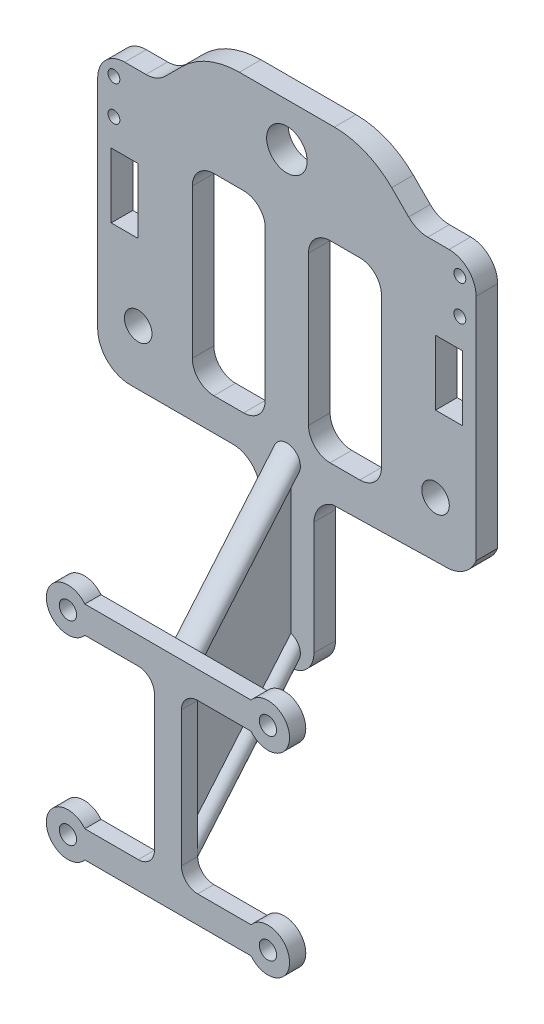
SolidWorks part; units mm, degrees
ref_plane "Спереди" through (0, 0, 0) normal (0, 0, 1) x (1, 0, 0)
ref_plane "Сверху" through (0, 0, 0) normal (0, 1, 0) x (1, 0, 0)
ref_plane "Справа" through (0, 0, 0) normal (1, 0, 0) x (0, 0, -1)
sketch "Model" plane through (0, 0, 0) normal (0, 0, 1) x (1, 0, 0)
  line L0 (-32.5, 1.0025) -> (-27.5, 1.0025)
  line L1 (-27.5, 1.0025) -> (-27.5, 11.0025)
  line L2 (-27.5, 11.0025) -> (-32.5, 11.0025)
  line L3 (-32.5, 11.0025) -> (-32.5, 1.0025)
  line L4 (32.5, 11.0025) -> (27.5, 11.0025)
  line L5 (27.5, 11.0025) -> (27.5, 1.0025)
  line L6 (27.5, 1.0025) -> (32.5, 1.0025)
  line L7 (32.5, 1.0025) -> (32.5, 11.0025)
  line L8 (-8.7868, 34.9967) -> (8.7868, 34.9967)
  line L9 (35, 8.7835) -> (35, -21.3839)
  line L11 (5, -30.1878) -> (5, -51.1878)
  line L12 (0.5, -55.6878) -> (-0.5, -55.6878)
  line L13 (-5, -51.1878) -> (-5, -30.1878)
  line L14 (8.4254, -25.669) -> (29, -25.1878)
  line L16 (-15.452, -19.1878) -> (15.452, -19.1878)
  line L17 (-17.5, -3.7682) -> (-17.5, -19.1878) construction
  line L18 (-17.5, -19.1878) -> (-15.452, -19.1878) construction
  line L19 (17.5, 14.8517) -> (17.5, 16.4118) construction
  line L20 (-27.5, 26.9967) -> (27.5, 26.9967) construction
  line L21 (17.5, 16.4118) -> (11.2964, 16.4118) construction
  line L22 (-27.5, 26.9967) -> (-27.5, 17.8476) construction
  line L23 (27.5, 26.9967) -> (27.5, -15.0033) construction
  line L24 (-17.5, -19.1878) -> (17.5, -19.1878)
  line L25 (-17.5, -19.1878) -> (-17.5, 16.4118)
  line L26 (-27.5, -15.0033) -> (27.5, -15.0033) construction
  line L27 (-17.5, 16.4118) -> (17.5, 16.4118)
  line L28 (17.5, -19.1878) -> (17.5, 16.4118)
  line L29 (-10, 16.0025) -> (10, 16.0025) construction
  line L30 (0, -15.0033) -> (0, -40.6878) construction
  line L31 (-5, -40.6878) -> (5, -40.6878) construction
  line L32 (0, -40.6878) -> (0, -51.1878) construction
  line L33 (0, -51.1878) -> (-0.5, -51.1878) construction
  line L34 (0, -51.1878) -> (0.5, -51.1878) construction
  line L35 (-10, -30.1878) -> (-0.5, -30.1878) construction
  line L36 (-0.5, -30.1878) -> (-0.5, -51.1878) construction
  line L37 (-30.6066, 19.3901) -> (-19.3934, 30.6033)
  line L38 (-35, 14.9967) -> (-35, 34.9967) construction
  line L39 (-35, 34.9967) -> (-15, 34.9967) construction
  line L40 (30.6066, 19.3901) -> (19.3934, 30.6033)
  line L41 (0, 34.9967) -> (0, 26.9967) construction
  line L42 (-35, 8.7835) -> (-35, -19.1878)
  line L43 (-29, -25.1878) -> (-10, -25.1878)
  line L44 (-32.5, 6.0025) -> (-27.5, 6.0025) construction
  line L45 (-27.5, 16.6674) -> (-27.5, -15.0033) construction
  line L46 (-30, 6.0025) -> (-30, -5.8427) construction
  circle A4 centre (-27.5, -15.0033) radius 2.55
  circle A5 centre (27.5, 26.9967) radius 3.556 construction
  circle A7 centre (27.5, -15.0033) radius 2.55
  circle A8 centre (0, 26.9967) radius 3.75
  arc A9 (35, 8.7835) -> (30.6066, 19.3901) centre (20, 8.7835) ccw
  arc A10 (-35, 8.7835) -> (-30.6066, 19.3901) centre (-20, 8.7835) cw
  arc A11 (19.3934, 30.6033) -> (8.7868, 34.9967) centre (8.7868, 19.9967) ccw
  arc A12 (-19.3934, 30.6033) -> (-8.7868, 34.9967) centre (-8.7868, 19.9967) cw
  arc A13 (-35, -19.1878) -> (-29, -25.1878) centre (-29, -19.1878) ccw
  arc A104 (29, -25.1878) -> (35, -21.3839) centre (29.4108, -19.2019) ccw
  arc A105 (8.4254, -25.669) -> (5, -30.1878) centre (9.9948, -30.4163) ccw
  arc A106 (0.5, -55.6878) -> (5, -51.1878) centre (0.5, -51.1878) ccw
  arc A107 (-5, -51.1878) -> (-0.5, -55.6878) centre (-0.5, -51.1878) ccw
  arc A108 (-5, -30.1878) -> (-10, -25.1878) centre (-10, -30.1878) ccw
  point P2 (0, 0)
  point P3 (0, 0)
  point P4 (0, 0)
  point P5 (0, 0)
  point P6 (0, 0)
  point P7 (0, 0)
  point P13 (0, 0)
  point P29 (6.0102, -27.3959)
  point P38 (35, 14.9967)
  point P44 (15, 34.9967)
  point P56 (0, 0)
  point P57 (0, 0)
  dimension "D2" = 7.5
  dimension "D6" = 5
  dimension "D7" = 4.5
  dimension "D8" = 4.5
  dimension "D12" = 15
  dimension "D14" = 6
  dimension "D15" = 6
  dimension "D3" = 42
  dimension "D4" = 10
  dimension "D5" = 5
  dimension "D9" = 21
  dimension "D10" = 20
  dimension "D11" = 20
  dimension "D13" = 8
extrude "Бобышка-Вытянуть1" add sketch "Model" along normal blind 4 contours A108 L13 A107 L12 A106 L11 A105 L14 A104 L9 L8 L3 L2 L1 L0 L7 L6 L5 L4 L28 L24 L16 L25 L27 A4 A5 A7 region at (0, 33.8511, 0)
sketch "Эскиз1" plane through (0, 0, 4) normal (0, 0, 1) x (1, 0, 0)
  line L0 (-27.5, -15.0033) -> (27.5, -15.0033) construction
  line L1 (0, -15.0033) -> (0, -22.5033) construction
  line L2 (0, -22.5033) -> (0, -52.5033) construction
  line L3 (0, -37.5033) -> (0.75, -37.5033) construction
  line L5 (0.75, -50.1185) -> (0.75, -24.8882)
  line L6 (-0.75, -50.1185) -> (-0.75, -24.8882)
  arc A0 (0.75, -24.8882) -> (-0.75, -24.8882) centre (0, -22.5033) ccw
  arc A1 (0.75, -50.1185) -> (-0.75, -50.1185) centre (0, -52.5033) cw
  point P14 (-0.75, -37.5033)
  dimension "D3" = 5
  dimension "D1" = 7.5
  dimension "D2" = 30
  dimension "D4" = 0.75
sketch "Эскиз2" plane through (0, 0, 0) normal (1, 0, 0) x (0, 0, -1)
  line L0 (-4, -22.5033) -> (-4, -45.0033) construction
  line L1 (-4, -45.0033) -> (-23, -45.0033) construction
  line L2 (-4, -22.5033) -> (-23, -45.0033) construction
  dimension "D1" = 22.5
  dimension "D2" = 19
sketch "Эскиз3" plane through (0, 0, 0) normal (1, 0, 0) x (0, 0, -1)
  line L0 (-4, -22.5033) -> (-23, -45.0033) construction
extrude "Бобышка-Вытянуть2" add sketch "Эскиз1" along direction (0, -0.764, 0.6452) on the side of the normal up to vertex (19 mm away) up to point (0, -45.0033, 23)
sketch "Эскиз4" plane through (0, 0, 23) normal (0, 0, 1) x (1, 0, 0)
  line L0 (0, -45.0033) -> (0, -83.0033) construction
  line L1 (0, -45.0033) -> (18.5, -45.0033) construction
  line L2 (9.25, -45.0033) -> (9.25, -47.5033) construction
  line L3 (15.3775, -47.5033) -> (5.5, -47.5033)
  line L4 (15.3775, -42.5033) -> (-15.3775, -42.5033)
  line L5 (0, -64.0033) -> (2.5, -64.0033) construction
  line L6 (2.5, -50.5033) -> (2.5, -64.0033)
  line L7 (-2.5, -50.5033) -> (-2.5, -64.0033)
  line L8 (-15.3775, -47.5033) -> (-5.5, -47.5033)
  line L9 (0, -63.0033) -> (7.4707, -63.0033) construction
  line L10 (7.4707, -63.0033) -> (7.4707, -45.0033) construction
  line L11 (-15.3775, -78.5033) -> (-5.5, -78.5033)
  line L12 (15.3775, -78.5033) -> (5.5, -78.5033)
  line L13 (15.3775, -83.5033) -> (-15.3775, -83.5033)
  line L14 (-2.5, -64.0033) -> (-2.5, -75.5033)
  line L15 (2.5, -64.0033) -> (2.5, -75.5033)
  line L16 (-2.5, -45.0033) -> (2.5, -45.0033) construction
  arc A0 (15.3775, -47.5033) -> (15.3775, -42.5033) centre (18.5, -45.0033) ccw
  circle A1 centre (18.5, -45.0033) radius 1.6
  arc A2 (2.5, -50.5033) -> (5.5, -47.5033) centre (5.5, -50.5033) cw
  arc A3 (-2.5, -50.5033) -> (-5.5, -47.5033) centre (-5.5, -50.5033) ccw
  circle A4 centre (-18.5, -45.0033) radius 1.6
  arc A5 (-15.3775, -47.5033) -> (-15.3775, -42.5033) centre (-18.5, -45.0033) cw
  circle A6 centre (-18.5, -81.0033) radius 1.6
  arc A7 (-2.5, -75.5033) -> (-5.5, -78.5033) centre (-5.5, -75.5033) cw
  arc A8 (2.5, -75.5033) -> (5.5, -78.5033) centre (5.5, -75.5033) ccw
  circle A9 centre (18.5, -81.0033) radius 1.6
  arc A10 (15.3775, -78.5033) -> (15.3775, -83.5033) centre (18.5, -81.0033) cw
  arc A11 (-15.3775, -78.5033) -> (-15.3775, -83.5033) centre (-18.5, -81.0033) ccw
  circle A12 centre (0, -45.0033) radius 2.5 construction
  point P25 (0, -42.5033)
  dimension "D2" = 8
  dimension "D3" = 3.2
  dimension "D6" = 3
  dimension "D1" = 18.5
  dimension "D4" = 2.5
  dimension "D5" = 2.5
  dimension "D7" = 18
extrude "Бобышка-Вытянуть3" add sketch "Эскиз4" along normal blind 3
fillet "Скругление1" radius 4 4 edges at (-17.5, 16.4118, 2) (17.5, 16.4118, 2) (17.5, -19.1878, 2) (-17.5, -19.1878, 2)
sketch "Эскиз5" plane through (0, 0, 4) normal (0, 0, 1) x (1, 0, 0)
  line L0 (-35, 8.7835) -> (-35, 26.0025)
  line L1 (-35, 8.7835) -> (-35, -19.1878) construction
  line L2 (-35, 26.0025) -> (-23.9942, 26.0025)
  line L3 (-30.6066, 19.3901) -> (-19.3934, 30.6033) construction
  line L4 (-23.9942, 26.0025) -> (-35, 8.7835)
  arc A0 (-30.6066, 19.3901) -> (-35, 8.7835) centre (-20, 8.7835) ccw construction
extrude "Бобышка-Вытянуть4" add sketch "Эскиз5" against normal blind 4
mirror "Зеркальное отражение1" about plane through (0, 0, 0) normal (1, 0, 0) of "Бобышка-Вытянуть4"
fillet "Скругление4" radius 5 4 edges at (23.9942, 26.0025, 2) (35, 26.0025, 2) (-23.9942, 26.0025, 2) (-35, 26.0025, 2)
sketch "Эскиз7" plane through (0, 0, 0) normal (0, 0, -1) x (-1, 0, 0)
  circle A0 centre (32, 22.7525) radius 1.1
  circle A1 centre (32, 16.2525) radius 1.1
  dimension "D1" = 2.2
  dimension "D2" = 2.2
extrude "Вырез-Вытянуть1" cut sketch "Эскиз7" against normal blind 4
mirror "Зеркальное отражение2" about plane through (0, 0, 0) normal (1, 0, 0) of "Вырез-Вытянуть1"
sketch "Эскиз8" plane through (0, 0, 4) normal (0, 0, 1) x (1, 0, 0)
  line L1 (-32.5, 1.0025) -> (-27.5, 1.0025)
  line L2 (-32.5, 1.0025) -> (-32.5, -0.9975)
  line L3 (-32.5, -0.9975) -> (-27.5, -0.9975)
  line L4 (-27.5, 1.0025) -> (-27.5, -0.9975)
  dimension "D1" = 2
extrude "Вырез-Вытянуть2" cut sketch "Эскиз8" against normal through all
mirror "Зеркальное отражение3" about plane through (0, 0, 0) normal (1, 0, 0) of "Вырез-Вытянуть2"
sketch "Эскиз9" plane through (0, 0, 4) normal (0, 0, 1) x (1, 0, 0)
  line L0 (0, -19.1878) -> (0, 16.4118) construction
  line L1 (-13.5, -19.1878) -> (13.5, -19.1878) construction
  line L2 (-13.5, 16.4118) -> (13.5, 16.4118) construction
  line L4 (-4, 19.1878) -> (4, 19.1878)
  line L5 (-4, 19.1878) -> (-4, -19.1878)
  line L6 (-4, -19.1878) -> (4, -19.1878)
  line L7 (4, 19.1878) -> (4, -19.1878)
  line L8 (-4, 19.1878) -> (4, -19.1878) construction
  line L9 (-4, -19.1878) -> (4, 19.1878) construction
  point P6 (0, 0)
  dimension "D1" = 8
extrude "Бобышка-Вытянуть5" add sketch "Эскиз9" against normal blind 4
fillet "Скругление5" radius 4 4 edges at (4, 16.4118, 2) (-4, 16.4118, 2) (4, -19.1878, 2) (-4, -19.1878, 2)
